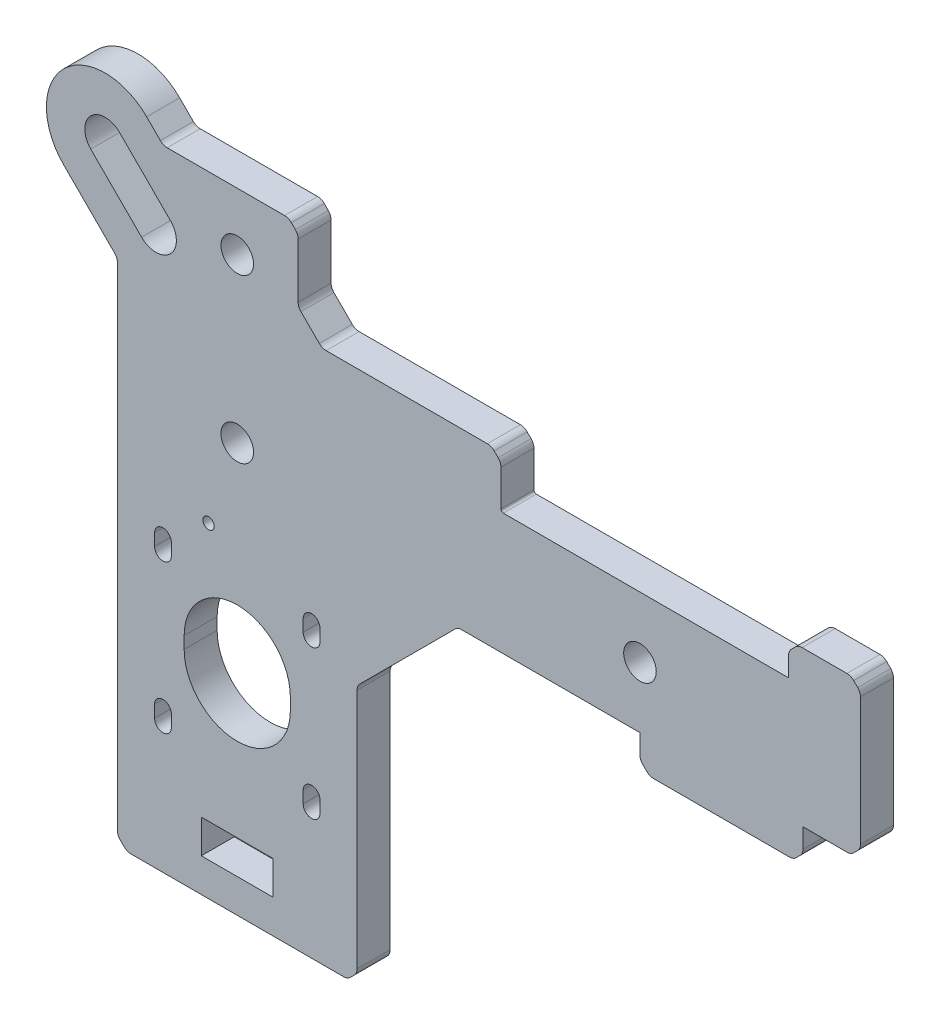
SolidWorks part; units mm, degrees
ref_plane "Front Plane" through (0, 0, 0) normal (0, 0, 1) x (1, 0, 0)
ref_plane "Top Plane" through (0, 0, 0) normal (0, 1, 0) x (1, 0, 0)
ref_plane "Right Plane" through (0, 0, 0) normal (1, 0, 0) x (0, 0, -1)
sketch "Sketch1" plane through (0, 0, 0) normal (0, 0, 1) x (1, 0, 0)
  line L1 (25, -65.675) -> (-25, -65.675)
  line L2 (25, -65.675) -> (25, 65.675)
  line L3 (25, 65.675) -> (-25, 65.675)
  line L4 (-25, -65.675) -> (-25, 65.675)
  line L5 (25, -65.675) -> (-25, 65.675) construction
  line L6 (25, 65.675) -> (-25, -65.675) construction
  point P0 (0, 0)
  dimension "D1" = 50
  dimension "D2" = 131.35
extrude "Boss-Extrude1" add sketch "Sketch1" along normal blind 6.88
sketch "Sketch2" plane through (0, 0, 6.88) normal (0, 0, 1) x (1, 0, 0)
  line L1 (15.5, -36.175) -> (-15.5, -36.175) construction
  line L2 (15.5, -36.175) -> (15.5, -5.175) construction
  line L3 (15.5, -5.175) -> (-15.5, -5.175) construction
  line L4 (-15.5, -36.175) -> (-15.5, -5.175) construction
  line L5 (15.5, -36.175) -> (-15.5, -5.175) construction
  line L6 (15.5, -5.175) -> (-15.5, -36.175) construction
  line L7 (-25, -65.675) -> (25, -65.675) construction
  line L8 (25, 65.675) -> (-25, 65.675) construction
  circle A0 centre (0, -20.675) radius 11.075
  circle A1 centre (-15.5, -5.175) radius 1.75
  circle A2 centre (-15.5, -36.175) radius 1.75
  circle A3 centre (15.5, -36.175) radius 1.75
  circle A4 centre (15.5, -5.175) radius 1.75
  circle A5 centre (0, 53.675) radius 3.4
  circle A6 centre (0, 19.675) radius 3.4
  dimension "D3" = 3.5
  dimension "D4" = 22.15
  dimension "D7" = 6.8
  dimension "D1" = 31
  dimension "D2" = 45
  dimension "D5" = 34
  dimension "D6" = 12
extrude "Cut-Extrude1" cut sketch "Sketch2" against normal through all
sketch "Sketch3" plane through (0, 0, 6.88) normal (0, 0, 1) x (1, 0, 0)
  line L0 (-25, -65.675) -> (25, -65.675) construction
  line L1 (7.5, -51.675) -> (-7.5, -51.675)
  line L2 (7.5, -51.675) -> (7.5, -58.675)
  line L3 (7.5, -58.675) -> (-7.5, -58.675)
  line L4 (-7.5, -51.675) -> (-7.5, -58.675)
  line L5 (7.5, -51.675) -> (-7.5, -58.675) construction
  line L6 (7.5, -58.675) -> (-7.5, -51.675) construction
  point P0 (0, -55.175)
  dimension "D1" = 15
  dimension "D2" = 7
  dimension "D3" = 7
extrude "Cut-Extrude2" cut sketch "Sketch3" against normal blind 6.88
sketch "Sketch4" plane through (0, 0, 6.88) normal (0, 0, 1) x (1, 0, 0)
  line L0 (25, 9.325) -> (130, 9.325)
  line L1 (25, -65.675) -> (25, 65.675) construction
  line L2 (130, 9.325) -> (130, 34.725)
  line L3 (130, 34.725) -> (25, 34.725)
  line L4 (25, 34.725) -> (25, 9.325)
  line L5 (-25, 65.675) -> (-25, -65.675) construction
  line L6 (130, 22.025) -> (0, 22.025) construction
  line L7 (-25, -65.675) -> (25, -65.675) construction
  dimension "D1" = 25.4
  dimension "D2" = 155
  dimension "D3" = 75
extrude "Boss-Extrude2" add sketch "Sketch4" against normal up to vertex (6.88 mm away) up to point (25, 65.675, 0)
sketch "Sketch5" plane through (0, 0, 6.88) normal (0, 0, 1) x (1, 0, 0)
  line L0 (118, 22.025) -> (84, 22.025) construction
  line L1 (84, 22.025) -> (0, 22.025) construction
  line L2 (130, 9.325) -> (130, 34.725) construction
  circle A0 centre (118, 22.025) radius 3.4
  circle A1 centre (84, 22.025) radius 3.4
  point P8 (130, 22.025)
  dimension "D3" = 6.8
  dimension "D1" = 12
  dimension "D2" = 34
extrude "Cut-Extrude3" cut sketch "Sketch5" against normal blind 6.88
sketch "Sketch6" plane through (0, 0, 6.88) normal (0, 0, 1) x (1, 0, 0)
  line L0 (25, 9.325) -> (130, 9.325) construction
  line L1 (84, 9.325) -> (118, 9.325)
  line L2 (84, 9.325) -> (84, 2.445)
  line L3 (84, 2.445) -> (118, 2.445)
  line L4 (118, 9.325) -> (118, 2.445)
  line L5 (84, 34.725) -> (84, 9.325) construction
  line L6 (118, 22.025) -> (118, 9.325) construction
  line L7 (130, 34.725) -> (25, 34.725) construction
  line L8 (130, 34.725) -> (115, 34.725)
  line L9 (130, 34.725) -> (130, 41.605)
  line L10 (130, 41.605) -> (115, 41.605)
  line L11 (115, 34.725) -> (115, 41.605)
  dimension "D1" = 6.88
  dimension "D2" = 15
  dimension "D3" = 34
extrude "Boss-Extrude3" add sketch "Sketch6" against normal up to vertex (6.88 mm away) up to point (130, 34.725, 0)
sketch "Sketch7" plane through (0, 0, 6.88) normal (0, 0, 1) x (1, 0, 0)
  line L0 (-25, 65.675) -> (-25, -65.675) construction
  line L5 (115, 34.725) -> (25, 34.725) construction
  line L8 (-25, 65.675) -> (-12.7, 65.675)
  line L9 (-25, 65.675) -> (-25, 45.605)
  line L10 (-25, 45.605) -> (-12.7, 45.605)
  line L11 (-12.7, 65.675) -> (-12.7, 45.605)
  line L12 (25, 65.675) -> (12.7, 65.675)
  line L13 (25, 65.675) -> (25, 45.605)
  line L14 (25, 45.605) -> (12.7, 45.605)
  line L15 (12.7, 65.675) -> (12.7, 45.605)
  dimension "D1" = 25.4
  dimension "D2" = 10.88
extrude "Cut-Extrude4" cut sketch "Sketch7" against normal blind 6.88
sketch "Sketch8" plane through (0, 0, 6.88) normal (0, 0, 1) x (1, 0, 0)
  line L0 (-6, 2.175) -> (6, 2.175) construction
  line L1 (12.7, 65.675) -> (-12.7, 65.675) construction
  line L2 (130, 9.325) -> (130, 41.605) construction
  line L3 (41.1, 28.025) -> (41.1, 16.025) construction
  line L4 (41.1, 22.025) -> (118, 22.025) construction
  circle A0 centre (-6, 2.175) radius 1.1811
  circle A1 centre (6, 2.175) radius 1.1811 construction
  circle A2 centre (41.1, 28.025) radius 1.1811 construction
  circle A3 centre (41.1, 16.025) radius 1.1811 construction
  point P4 (0, 2.175)
  dimension "D1" = 2.3622
  dimension "D2" = 12
  dimension "D3" = 63.5
  dimension "D4" = 12
  dimension "D5" = 88.9
extrude "Cut-Extrude5" cut sketch "Sketch8" against normal blind 6.88
sketch "Sketch9" plane through (0, 0, 6.88) normal (0, 0, 1) x (1, 0, 0)
  circle A0 centre (15.5, -36.175) radius 3
  circle A1 centre (-15.5, -36.175) radius 3
  circle A2 centre (-15.5, -5.175) radius 3
  circle A4 centre (15.5, -5.175) radius 3
  dimension "D1" = 6
extrude "Cut-Extrude6" [suppressed] cut sketch "Sketch9" against normal blind 6.88
sketch "Sketch10" plane through (0, 0, 6.88) normal (0, 0, 1) x (1, 0, 0)
  circle A0 centre (0, -20.675) radius 13
  dimension "D1" = 26
extrude "Boss-Extrude4" [suppressed] add sketch "Sketch10" against normal up to vertex up to point (-25, -65.675, 0)
sketch "Sketch11" plane through (0, 0, 6.88) normal (0, 0, 1) x (1, 0, 0)
  line L0 (115, 34.725) -> (25, 34.725) construction
  line L1 (25, 45.605) -> (55, 45.605)
  line L2 (25, 45.605) -> (25, 34.725)
  line L3 (25, 34.725) -> (55, 34.725)
  line L4 (55, 45.605) -> (55, 34.725)
  dimension "D1" = 30
extrude "Boss-Extrude5" add sketch "Sketch11" against normal up to vertex (6.88 mm away) up to point (12.7, 45.605, 0)
chamfer "Chamfer2" distance 21 angle 45 1 edges at (25, 9.325, 3.44)
sketch "Sketch12" plane through (0, 0, 6.88) normal (0, 0, 1) x (1, 0, 0)
  line L0 (-15.5, -5.175) -> (-15.5, -7.675) construction
  line L1 (-13.75, -5.175) -> (-13.75, -7.675)
  line L2 (-17.25, -5.175) -> (-17.25, -7.675)
  line L3 (15.5, -5.175) -> (15.5, -7.675) construction
  line L4 (17.25, -5.175) -> (17.25, -7.675)
  line L5 (13.75, -5.175) -> (13.75, -7.675)
  line L6 (-15.5, -36.175) -> (-15.5, -38.675) construction
  line L7 (-13.75, -36.175) -> (-13.75, -38.675)
  line L8 (-17.25, -36.175) -> (-17.25, -38.675)
  line L9 (15.5, -36.175) -> (15.5, -38.675) construction
  line L10 (17.25, -36.175) -> (17.25, -38.675)
  line L11 (13.75, -36.175) -> (13.75, -38.675)
  line L12 (0, -20.675) -> (0, -23.175) construction
  line L13 (11.075, -20.675) -> (11.075, -23.175)
  line L14 (-11.075, -20.675) -> (-11.075, -23.175)
  arc A0 (-13.75, -5.175) -> (-17.25, -5.175) centre (-15.5, -5.175) ccw
  arc A1 (-17.25, -7.675) -> (-13.75, -7.675) centre (-15.5, -7.675) ccw
  circle A2 centre (-15.5, -5.175) radius 1.75 construction
  arc A3 (17.25, -5.175) -> (13.75, -5.175) centre (15.5, -5.175) ccw
  arc A4 (13.75, -7.675) -> (17.25, -7.675) centre (15.5, -7.675) ccw
  arc A5 (-13.75, -36.175) -> (-17.25, -36.175) centre (-15.5, -36.175) ccw
  arc A6 (-17.25, -38.675) -> (-13.75, -38.675) centre (-15.5, -38.675) ccw
  arc A7 (17.25, -36.175) -> (13.75, -36.175) centre (15.5, -36.175) ccw
  arc A8 (13.75, -38.675) -> (17.25, -38.675) centre (15.5, -38.675) ccw
  arc A9 (11.075, -20.675) -> (-11.075, -20.675) centre (0, -20.675) ccw
  arc A10 (-11.075, -23.175) -> (11.075, -23.175) centre (0, -23.175) ccw
  circle A11 centre (0, -20.675) radius 11.075 construction
  point P3 (-15.5, -6.425)
  point P12 (15.5, -6.425)
  point P19 (-15.5, -37.425)
  point P26 (15.5, -37.425)
  point P35 (0, -21.925)
  dimension "D1" = 2.5
  dimension "D2" = 2.5
extrude "Cut-Extrude7" cut sketch "Sketch12" against normal blind 10
sketch "Sketch13" [suppressed] plane through (0, 0, 6.88) normal (0, 0, 1) x (1, 0, 0)
  line L0 (-15.5, -5.175) -> (-15.5, -7.675) construction
  line L1 (-12.5, -5.175) -> (-12.5, -7.675)
  line L2 (-18.5, -5.175) -> (-18.5, -7.675)
  line L3 (15.5, -5.175) -> (15.5, -7.675) construction
  line L4 (18.5, -5.175) -> (18.5, -7.675)
  line L5 (12.5, -5.175) -> (12.5, -7.675)
  line L6 (15.5, -36.175) -> (15.5, -38.675) construction
  line L7 (18.5, -36.175) -> (18.5, -38.675)
  line L8 (12.5, -36.175) -> (12.5, -38.675)
  line L9 (-15.5, -36.175) -> (-15.5, -38.675) construction
  line L10 (-12.5, -36.175) -> (-12.5, -38.675)
  line L11 (-18.5, -36.175) -> (-18.5, -38.675)
  arc A0 (-12.5, -5.175) -> (-18.5, -5.175) centre (-15.5, -5.175) ccw
  arc A1 (-18.5, -7.675) -> (-12.5, -7.675) centre (-15.5, -7.675) ccw
  circle A2 centre (-15.5, -5.175) radius 3 construction
  arc A3 (18.5, -5.175) -> (12.5, -5.175) centre (15.5, -5.175) ccw
  arc A4 (12.5, -7.675) -> (18.5, -7.675) centre (15.5, -7.675) ccw
  arc A5 (18.5, -36.175) -> (12.5, -36.175) centre (15.5, -36.175) ccw
  arc A6 (12.5, -38.675) -> (18.5, -38.675) centre (15.5, -38.675) ccw
  arc A7 (-12.5, -36.175) -> (-18.5, -36.175) centre (-15.5, -36.175) ccw
  arc A8 (-18.5, -38.675) -> (-12.5, -38.675) centre (-15.5, -38.675) ccw
  point P3 (-15.5, -6.425)
  point P12 (15.5, -6.425)
  point P19 (15.5, -37.425)
  point P26 (-15.5, -37.425)
  dimension "D1" = 2.5
extrude "Cut-Extrude8" [suppressed] cut sketch "Sketch13" against normal blind 10
sketch "Sketch14" [suppressed] plane through (0, 0, 6.88) normal (0, 0, 1) x (1, 0, 0)
  line L0 (2.5, -7) -> (-2.5, -7) construction
  line L1 (2.5, -9) -> (-2.5, -9)
  line L2 (2.5, -5) -> (-2.5, -5)
  arc A0 (2.5, -9) -> (2.5, -5) centre (2.5, -7) ccw
  arc A1 (-2.5, -5) -> (-2.5, -9) centre (-2.5, -7) ccw
  point P2 (0, -7)
  dimension "D1" = 4
  dimension "D2" = 5
  dimension "D3" = 7
extrude "Cut-Extrude9" [suppressed] cut sketch "Sketch14" against normal through all
chamfer "Chamfer5" distance 5 angle 45 2 edges at (-12.7, 45.605, 3.44) (12.7, 45.605, 3.44)
chamfer "Chamfer3" distance 2 angle 45 11 edges at (-25, -65.675, 3.44) (84, 2.445, 3.44) (118, 2.445, 3.44) (130, 9.325, 3.44) (115, 41.605, 3.44) (130, 41.605, 3.44) (-25, 45.605, 3.44) (-12.7, 65.675, 3.44) (12.7, 65.675, 3.44) (55, 45.605, 3.44) (25, -65.675, 3.44)
sketch "Sketch15" [suppressed] plane through (0, 0, 6.88) normal (0, 0, 1) x (1, 0, 0)
  circle A0 centre (84, 22.025) radius 7.2715
extrude "Boss-Extrude6" [suppressed] add sketch "Sketch15" against normal up to vertex up to point (55, 34.725, 0)
sketch "Sketch16" plane through (0, 0, 6.88) normal (0, 0, 1) x (1, 0, 0)
  circle A0 centre (118, 22.025) radius 7.069
extrude "Boss-Extrude7" add sketch "Sketch16" against normal up to vertex (6.88 mm away) up to point (55, 34.725, 0)
sketch "Sketch17" plane through (0, 0, 0) normal (0, 0, 1) x (1, 0, 0)
  line L0 (-16.95, 49.855) -> (-27.5566, 60.4616) construction
  line L2 (-15.2, 48.105) -> (-16.95, 49.855) construction
  line L5 (-12.7, 50.605) -> (-17.7, 45.605) construction
  line L48 (-12.7, 50.605) -> (-12.7, 63.675) construction
  line L54 (-25.6121, 41.1929) -> (-36.2187, 51.7995)
  line L55 (-8.2879, 58.5171) -> (-18.8945, 69.1237)
  line L56 (-27.5566, 60.4616) -> (-16.95, 49.855) construction
  line L57 (-24.5514, 63.4668) -> (-13.9448, 52.8602)
  line L58 (-30.5618, 57.4564) -> (-19.9552, 46.8498)
  line L59 (-10.7, 65.675) -> (-15.4459, 65.675)
  arc A8 (-25.6121, 41.1929) -> (-8.2879, 58.5171) centre (-16.95, 49.855) ccw
  arc A9 (-18.8945, 69.1237) -> (-36.2187, 51.7995) centre (-27.5566, 60.4616) ccw
  arc A10 (-24.5514, 63.4668) -> (-30.5618, 57.4564) centre (-27.5566, 60.4616) ccw
  arc A11 (-19.9552, 46.8498) -> (-13.9448, 52.8602) centre (-16.95, 49.855) ccw
  point P4 (-22.2533, 55.1583)
  point P9 (-22.2533, 55.1583)
  point P16 (-13.5912, 63.8204)
  dimension "D1" = 8.5
  dimension "D2" = 8
  dimension "D3" = 15
extrude "Cut-Extrude10" cut sketch "Sketch17" along normal blind 10 contours L58 A11 L57 A10 region at (-22.2533, 55.1583, 0)
sketch "Sketch18" plane through (0, 0, 0) normal (0, 0, -1) x (-1, 0, 0)
  line L0 (10.7, 65.675) -> (15.4459, 65.675) construction
  line L1 (10.7, 65.675) -> (15.4459, 65.675)
  line L2 (24.5514, 63.4668) -> (13.9448, 52.8602)
  line L3 (19.9552, 46.8498) -> (30.5618, 57.4564)
  line L4 (24.5514, 63.4668) -> (13.9448, 52.8602)
  line L5 (19.9552, 46.8498) -> (30.5618, 57.4564)
  line L6 (25.6121, 41.1929) -> (36.2187, 51.7995)
  line L7 (18.8945, 69.1237) -> (8.2879, 58.5171)
  line L8 (25.6121, 41.1929) -> (36.2187, 51.7995)
  line L9 (18.8945, 69.1237) -> (15.4459, 65.675)
  line L10 (10.7, 65.675) -> (10.7, 60.9291)
  line L11 (10.7, 60.9291) -> (8.2879, 58.5171)
  arc A2 (13.9448, 52.8602) -> (19.9552, 46.8498) centre (16.95, 49.855) ccw
  arc A3 (30.5618, 57.4564) -> (24.5514, 63.4668) centre (27.5566, 60.4616) ccw
  arc A4 (13.9448, 52.8602) -> (19.9552, 46.8498) centre (16.95, 49.855) ccw
  arc A5 (30.5618, 57.4564) -> (24.5514, 63.4668) centre (27.5566, 60.4616) ccw
  arc A6 (36.2187, 51.7995) -> (18.8945, 69.1237) centre (27.5566, 60.4616) ccw
  arc A7 (8.2879, 58.5171) -> (25.6121, 41.1929) centre (16.95, 49.855) ccw
  arc A8 (36.2187, 51.7995) -> (18.8945, 69.1237) centre (27.5566, 60.4616) ccw
  arc A9 (8.2879, 58.5171) -> (25.6121, 41.1929) centre (16.95, 49.855) ccw
  dimension "D1" = 0
  dimension "D2" = 0
extrude "Boss-Extrude8" add sketch "Sketch18" against normal up to vertex (6.88 mm away) up to point (10.7, 65.675, 6.88)
fillet "Fillet1" radius 2 24 edges at (-25, -63.675, 3.44) (-23, -65.675, 3.44) (23, -65.675, 3.44) (25, -63.675, 3.44) (25, -11.675, 3.44) (46, 9.325, 3.44) (84, 4.445, 3.44) (86, 2.445, 3.44) (116, 2.445, 3.44) (118, 4.445, 3.44) (128, 9.325, 3.44) (130, 11.325, 3.44) (130, 39.605, 3.44) (128, 41.605, 3.44) (117, 41.605, 3.44) (115, 39.605, 3.44) (55, 43.605, 3.44) (53, 45.605, 3.44) (17.7, 45.605, 3.44) (12.7, 50.605, 3.44) (-15.4459, 65.675, 3.44) (-25, 40.6214, 3.44) (12.7, 63.675, 3.44) (10.7, 65.675, 3.44)
fillet "Fillet2" [suppressed] radius 0.5
fillet "Fillet3" radius 0.5 1 edges at (55, 34.725, 3.44)
